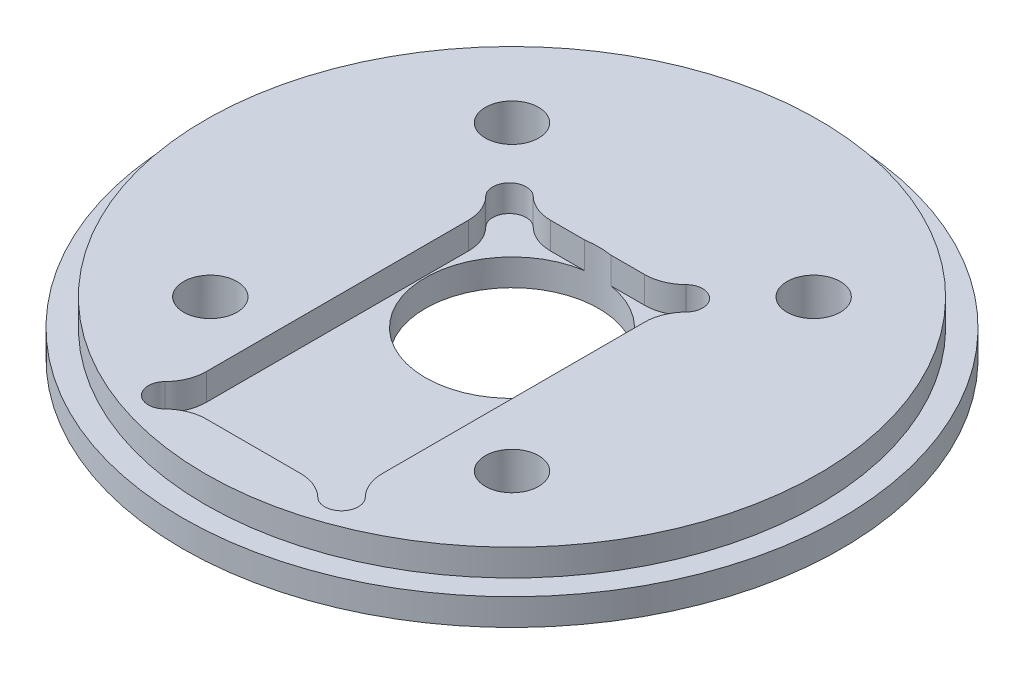
SolidWorks part; units mm, degrees
ref_plane "Front Plane" through (0, 0, 0) normal (0, 0, 1) x (1, 0, 0)
ref_plane "Top Plane" through (0, 0, 0) normal (0, 1, 0) x (1, 0, 0)
ref_plane "Right Plane" through (0, 0, 0) normal (1, 0, 0) x (0, 0, -1)
sketch "Sketch2" plane through (0, 0, 0) normal (0, 1, 0) x (1, 0, 0)
  circle A0 centre (0, 0) radius 39.243
  dimension "D1" = 78.486
extrude "Boss-Extrude1" add sketch "Sketch2" along normal blind 6.35
sketch "Sketch4" plane through (0, 6.35, 0) normal (0, 1, 0) x (1, 0, 0)
  circle A0 centre (0, 0) radius 36.5125
  circle A1 centre (0, 0) radius 39.243 construction
  circle A2 centre (0, 0) radius 39.243
  dimension "D1" = 73.025
extrude "Cut-Extrude1" cut sketch "Sketch4" against normal blind 3.175
sketch "Sketch5" plane through (0, 6.35, 0) normal (0, 1, 0) x (1, 0, 0)
  line L0 (17.9605, 17.9605) -> (-17.9605, -17.9605) construction
  line L1 (-17.9605, 17.9605) -> (17.9605, -17.9605) construction
  line L2 (-1000, 0) -> (49000, 0) construction
  point P1 (-17.9605, -17.9605)
  point P2 (17.9605, 17.9605)
  point P5 (17.9605, -17.9605)
  point P6 (-17.9605, 17.9605)
  dimension "D1" = 50.8
  dimension "D2" = 45
hole_wizard "1/4 (0.25) Diameter Hole1" positions "Sketch5" profile "Sketch6" hole size "1/4" standard "ANSI Inch" end condition through all
sketch "Sketch6" plane through (-17.9605, 6.35, -17.9605) normal (1, 0, 0) x (0, 0, 1)
  line L0 (0, 0) -> (0, 6.35)
  line L1 (0, 6.35) -> (3.175, 6.35)
  line L2 (3.175, 6.35) -> (3.175, 0)
  line L5 (3.175, 0) -> (0, 0)
  line L11 (0, -6.35) -> (0, 107.95) construction
  dimension "Thru Hole Dia." = 6.35
  dimension "Thru Hole Depth" = 6.35
sketch "Sketch7" plane through (0, 6.35, 0) normal (0, 1, 0) x (1, 0, 0)
  point P0 (0, 0)
hole_wizard "13/16 (0.8125) Diameter Hole1" positions "Sketch7" profile "Sketch8" hole size "13/16" standard "ANSI Inch" end condition through all
sketch "Sketch8" plane through (0, 6.35, 0) normal (1, 0, 0) x (0, 0, 1)
  line L0 (0, 0) -> (0, 6.35)
  line L1 (0, 6.35) -> (10.3187, 6.35)
  line L2 (10.3187, 6.35) -> (10.3187, 0)
  line L5 (10.3187, 0) -> (0, 0)
  line L11 (0, -6.35) -> (0, 107.95) construction
  dimension "Thru Hole Dia." = 20.6375
  dimension "Thru Hole Depth" = 6.35
sketch "Sketch11" plane through (0, 6.35, 0) normal (0, 1, 0) x (1, 0, 0)
  line L0 (0, -3.4925) -> (0, 3.4925) construction
  line L1 (-5.601, 10.2) -> (5.601, 10.2)
  line L2 (-10.5, 5.301) -> (-10.5, -25.901)
  line L3 (-5.601, -30.8) -> (5.601, -30.8)
  line L4 (10.5, 5.301) -> (10.5, -25.901)
  line L5 (-10.5, 10.2) -> (10.5, -30.8) construction
  line L6 (-10.5, -30.8) -> (10.5, 10.2) construction
  line L7 (0, -10.3) -> (7.6415, -10.3) construction
  line L8 (-10.5, -30.8) -> (-8.5, -30.8) construction
  line L9 (-10.5, -28.8) -> (-10.5, -30.8) construction
  line L10 (-10.5, 10.2) -> (-8.5, 10.2) construction
  line L11 (-10.5, 10.2) -> (-10.5, 8.2) construction
  line L12 (8.5, -30.8) -> (10.5, -30.8) construction
  line L13 (10.5, -28.8) -> (10.5, -30.8) construction
  line L14 (8.5, 10.2) -> (10.5, 10.2) construction
  line L15 (10.5, 10.2) -> (10.5, 8.2) construction
  arc A0 (-11.9286, -29.4003) -> (-9.1003, -32.2286) centre (-10.5, -30.8) ccw
  arc A1 (11.9286, -29.4003) -> (9.1003, -32.2286) centre (10.5, -30.8) cw
  arc A2 (11.9286, 8.8003) -> (9.1003, 11.6286) centre (10.5, 10.2) ccw
  arc A3 (-11.9286, 8.8003) -> (-9.1003, 11.6286) centre (-10.5, 10.2) cw
  arc A4 (-11.9286, -29.4003) -> (-10.5, -25.901) centre (-15.5, -25.901) ccw
  arc A5 (-9.1003, -32.2286) -> (-5.601, -30.8) centre (-5.601, -35.8) cw
  arc A6 (11.9286, -29.4003) -> (10.5, -25.901) centre (15.5, -25.901) cw
  arc A7 (9.1003, -32.2286) -> (5.601, -30.8) centre (5.601, -35.8) ccw
  arc A8 (11.9286, 8.8003) -> (10.5, 5.301) centre (15.5, 5.301) ccw
  arc A9 (9.1003, 11.6286) -> (5.601, 10.2) centre (5.601, 15.2) cw
  arc A10 (-9.1003, 11.6286) -> (-5.601, 10.2) centre (-5.601, 15.2) ccw
  arc A11 (-11.9286, 8.8003) -> (-10.5, 5.301) centre (-15.5, 5.301) cw
  point P0 (0, 0)
  point P1 (0, -10.3)
  dimension "D4" = 2
  dimension "D5" = 5
  dimension "D1" = 10.2
  dimension "D2" = 21
  dimension "D3" = 41
extrude "Cut-Extrude3" cut sketch "Sketch11" against normal blind 3.175
sketch "Sketch9" plane through (0, 0, 0) normal (0, -1, 0) x (1, 0, 0)
  circle A0 centre (-17.9605, -17.9605) radius 3.175 construction
  circle A1 centre (17.9605, -17.9605) radius 3.175 construction
  circle A2 centre (17.9605, 17.9605) radius 3.175 construction
  circle A3 centre (-17.9605, 17.9605) radius 3.175 construction
  circle A4 centre (-17.9605, -17.9605) radius 3.175 construction
  circle A5 centre (17.9605, -17.9605) radius 3.175 construction
  circle A6 centre (17.9605, 17.9605) radius 3.175 construction
  circle A7 centre (-17.9605, 17.9605) radius 3.175 construction
  circle A8 centre (-17.9605, 17.9605) radius 6.0325
  circle A9 centre (17.9605, 17.9605) radius 6.0325
  circle A10 centre (17.9605, -17.9605) radius 6.0325
  circle A11 centre (-17.9605, -17.9605) radius 6.0325
  point P13 (-17.9605, 17.9605)
  point P14 (17.9605, 17.9605)
  point P15 (17.9605, -17.9605)
  point P16 (-17.9605, -17.9605)
  dimension "D1" = 12.065
extrude "Cut-Extrude2" cut sketch "Sketch9" against normal blind 1.5875
equation "\"AIRFRAME_OD\"= 3.091in"
equation "\"AIRFRAME_ID\"= 3.00in"
equation "\"FLAT_T\"= 0.125in"
equation "\"NOSE_EXP_L\"= 3.5in"
equation "\"NOSE_SHOULDER_L\"= 5in"
equation "\"MAIN_L\"= 30in"
equation "\"RECO_COUP_L\"= 6in"
equation "\"RECO_SWITCH_L\"= 1.5in"
equation "\"DROGUE_L\"= 14in"
equation "\"ATS_FORE_COUP_L\"= 4in"
equation "\"ATS_AFT_COUP_L\"= 2.5in"
equation "\"LOWER_L\"= 16in"
equation "\"FIN_N\"= 4"
equation "\"CR_AFT_X\"= 0.5in"
equation "\"CR_FORE_X\"= 6in"
equation "\"D1@Boss-Extrude1\"=2*\"FLAT_T\""
equation "\"COUPLER_OD\"= 2.998in"
equation "\"COUPLER_ID\"= 2.875in"
equation "\"RECO_ROD_X\"= 1.5in"
equation "\"ATS_ROD_X\"= 2in"
equation "\"FIN_ROOT\"= 5in"
equation "\"FIN_X\"= 0.75in"
equation "\"MOTOR_OD\"= 2.25in"
equation "\"MOTOR_ID\"= 2.126in"
equation "\"MOTOR_L\"= 8in"
equation "\"MOTOR_LOWER_X\"= 0.5in"
equation "\"D1@Sketch4\"=\"COUPLER_ID\""
equation "\"D1@Cut-Extrude1\"=\"FLAT_T\""
equation "\"D1@Cut-Extrude3\"=\"FLAT_T\""
